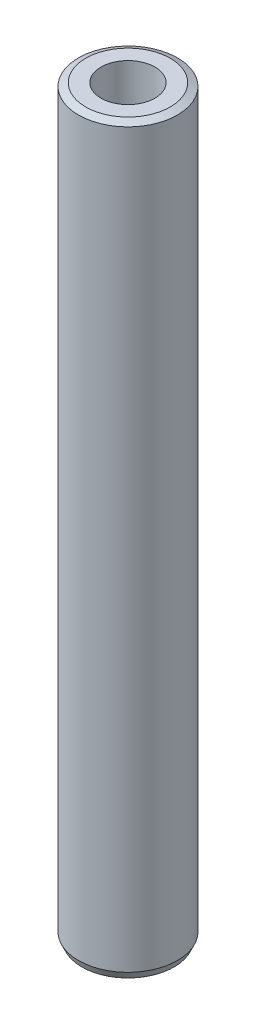
SolidWorks part; units mm, degrees
ref_plane "Front Plane" through (0, 0, 0) normal (0, 0, 1) x (1, 0, 0)
ref_plane "Top Plane" through (0, 0, 0) normal (0, 1, 0) x (1, 0, 0)
ref_plane "Right Plane" through (0, 0, 0) normal (1, 0, 0) x (0, 0, -1)
sketch "Sketch1" plane through (0, 0, 0) normal (0, 1, 0) x (1, 0, 0)
  circle A0 centre (0, 0) radius 40
  dimension "SHAFT_OD" = 80
extrude "Boss-Extrude1" add sketch "Sketch1" along normal blind 600
sketch "Sketch2" plane through (0, 0, 0) normal (0, 1, 0) x (1, 0, 0)
  circle A0 centre (0, 0) radius 21.8086
  dimension "BORE_D" = 43.6172
extrude "Cut-Extrude1" cut sketch "Sketch2" along normal through all
chamfer "Chamfer1" distance 2.6812 angle 65.47 2 edges at (0, 600, 40) (0, 0, 40) first distance on face at (0, 600, 40) first distance on face at (0, 0, 21.8086)
